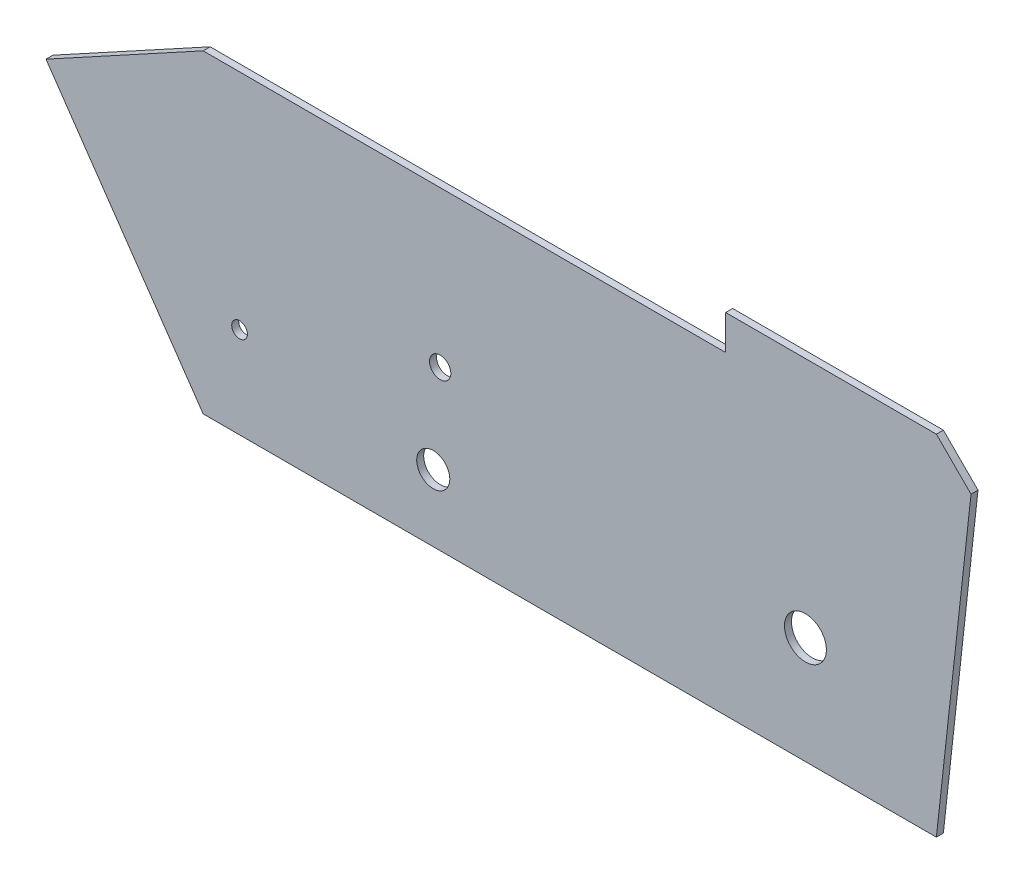
SolidWorks part; units mm, degrees
ref_plane "Front Plane" through (0, 0, 0) normal (0, 0, 1) x (1, 0, 0)
ref_plane "Top Plane" through (0, 0, 0) normal (0, 1, 0) x (1, 0, 0)
ref_plane "Right Plane" through (0, 0, 0) normal (1, 0, 0) x (0, 0, -1)
sketch "Sketch1" plane through (0, 0, 0) normal (0, 0, 1) x (1, 0, 0)
  line L0 (192.0393, 88.9838) -> (201.963, 79.0601)
  line L5 (201.963, 79.0601) -> (192.0393, -11.0162)
  line L6 (192.0393, -11.0162) -> (-18.008, -11.0162)
  line L8 (-18.008, 79.0601) -> (131.6712, 79.0601)
  line L9 (131.6712, 79.0601) -> (131.6712, 88.9838)
  line L10 (131.6712, 88.9838) -> (192.0393, 88.9838)
  line L11 (-18.008, 79.0601) -> (-63.037, 54.4726)
  line L12 (-63.037, 54.4726) -> (-18.008, -11.0162)
extrude "Boss-Extrude1" add sketch "Sketch1" along normal blind 2
sketch "Sketch2" plane through (0, 0, 2) normal (0, 0, 1) x (1, 0, 0)
  circle A0 centre (154.5233, 19.6951) radius 6
  dimension "D1" = 12
extrude "Cut-Extrude1" cut sketch "Sketch2" against normal blind 10
sketch "Sketch3" plane through (0, 0, 2) normal (0, 0, 1) x (1, 0, 0)
  circle A0 centre (49.8867, 34.4676) radius 3.05
extrude "Cut-Extrude2" cut sketch "Sketch3" against normal blind 10
sketch "Sketch4" plane through (0, 0, 2) normal (0, 0, 1) x (1, 0, 0)
  circle A0 centre (-7.5862, 15.0785) radius 2.2503
extrude "Cut-Extrude3" cut sketch "Sketch4" against normal blind 10
sketch "Sketch5" plane through (0, 0, 2) normal (0, 0, 1) x (1, 0, 0)
  circle A0 centre (47.9037, 8.1196) radius 4.7404
extrude "Cut-Extrude4" cut sketch "Sketch5" against normal blind 10
